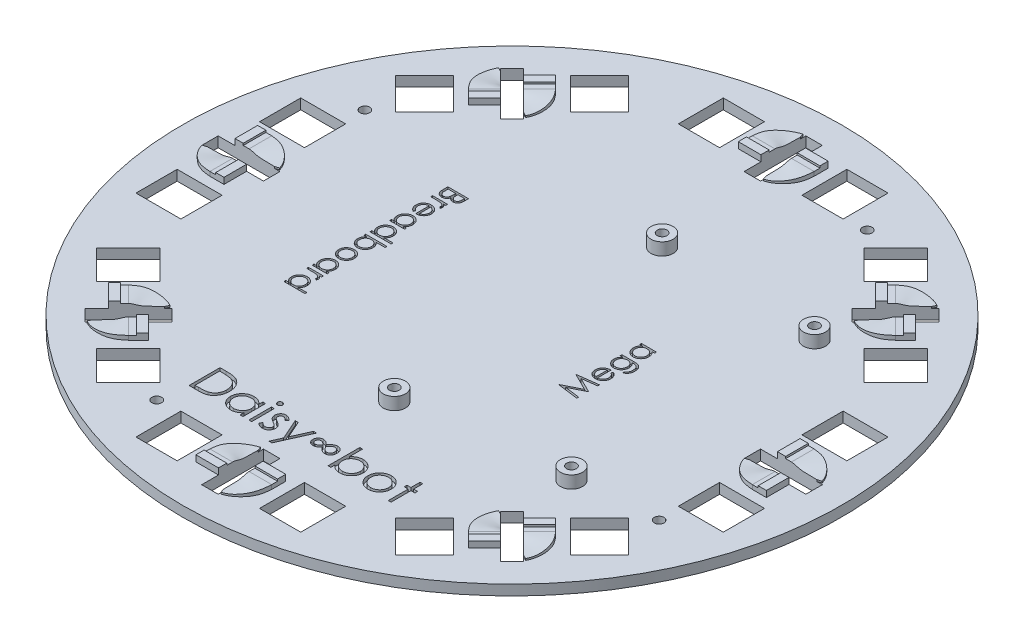
SolidWorks part; units mm, degrees
ref_plane "Front" through (0, 0, 0) normal (0, 0, 1) x (1, 0, 0)
ref_plane "Top" through (0, 0, 0) normal (0, 1, 0) x (1, 0, 0)
ref_plane "Right" through (0, 0, 0) normal (1, 0, 0) x (0, 0, -1)
sketch "Sketch1" plane through (0, 0, 0) normal (0, 1, 0) x (1, 0, 0)
  circle A0 centre (0, 0) radius 101.6
  dimension "D1" = 203.2
extrude "Base" add sketch "Sketch1" along normal blind 3.175 contours A0
sketch "Sketch2" plane through (0, 3.175, 0) normal (0, 1, 0) x (1, 0, 0)
  line L1 (-2.54, -93.1333) -> (2.54, -93.1333)
  line L2 (-2.54, -93.1333) -> (-2.54, -74.0833)
  line L3 (-2.54, -74.0833) -> (2.54, -74.0833)
  line L4 (2.54, -93.1333) -> (2.54, -74.0833)
  point P4 (0, -74.0833)
  dimension "D1" = 5.08
  dimension "D2" = 19.05
  dimension "D3" = 93.1333
extrude "Cut-Extrude1" cut sketch "Sketch2" against normal up to next and the other way through all contours L1 L4 L3 L2
sketch "Sketch4" plane through (0, 3.175, 0) normal (0, 1, 0) x (1, 0, 0)
  line L0 (0, -83.6083) -> (-2.9434, -74.5495) construction
  line L1 (-2.9434, -74.5495) -> (0, -83.6083) construction
  line L2 (0, -83.6083) -> (-5.5987, -75.9024) construction
  line L3 (0, -83.6083) -> (-7.7059, -78.0097) construction
  line L4 (0, -83.6083) -> (-9.0588, -80.6649) construction
  line L5 (0, -83.6083) -> (-9.525, -83.6083) construction
  line L9 (2.54, -74.0833) -> (-2.54, -74.0833) construction
  line L10 (2.54, -74.0833) -> (2.54, -93.1333) construction
  line L11 (-2.54, -74.0833) -> (-2.54, -93.1333) construction
  line L12 (2.54, -93.1333) -> (-2.54, -93.1333) construction
  circle A0 centre (0, -83.6083) radius 9.525 construction
  point P16 (0, -74.0833)
  point P19 (2.54, -83.6083)
  dimension "D1" = 18
  dimension "D2" = 18
  dimension "D3" = 18
  dimension "D4" = 18
  dimension "D5" = 18
ref_plane "Plane1" through (-24.5719, 0, 7.9839) normal (0.9511, 0, -0.309) x (-0.309, 0, -0.9511)
ref_plane "Plane2" through (-39.7581, 0, 28.886) normal (0.809, 0, -0.5878) x (-0.5878, 0, -0.809)
ref_plane "Plane3" through (-39.7581, 0, 54.7224) normal (0.5878, 0, -0.809) x (-0.809, 0, -0.5878)
ref_plane "Plane4" through (-24.5719, 0, 75.6244) normal (0.309, 0, -0.9511) x (-0.9511, 0, -0.309)
ref_plane "Plane5" through (0, 0, 83.6083) normal (0, 0, -1) x (-1, 0, 0)
sketch "Sketch5" plane through (-24.5719, 0, 7.9839) normal (0.9511, 0, -0.309) x (-0.309, 0, -0.9511)
  line L0 (-69.6725, 3.175) -> (-87.7902, 3.175) construction
  line L1 (-71.2966, 3.175) -> (-69.9913, 3.175)
  line L2 (-71.2966, 3.175) -> (-71.2966, 3.683)
  line L3 (-71.2966, 3.683) -> (-69.9913, 3.683)
  line L4 (-69.9913, 3.175) -> (-69.9913, 3.683)
  dimension "D2" = 0.508
sketch "Sketch6" plane through (-39.7581, 0, 28.886) normal (0.809, 0, -0.5878) x (-0.5878, 0, -0.809)
  line L0 (-58.4417, 3.175) -> (-73.8535, 3.175) construction
  line L1 (-63.3193, 3.175) -> (-58.1156, 3.175)
  line L2 (-63.3193, 3.175) -> (-63.3193, 3.775)
  line L3 (-63.3193, 3.775) -> (-58.1156, 3.775)
  line L4 (-58.1156, 3.175) -> (-58.1156, 3.775)
  dimension "D2" = 0.6
sketch "Sketch7" plane through (-39.7581, 0, 54.7224) normal (0.5878, 0, -0.809) x (-0.809, 0, -0.5878)
  line L0 (-41.4902, 3.175) -> (-52.6875, 3.175) construction
  line L1 (-46.0041, 3.175) -> (-39.6187, 3.175)
  line L2 (-46.0041, 3.175) -> (-46.0041, 4.075)
  line L3 (-46.0041, 4.075) -> (-39.6187, 4.075)
  line L4 (-39.6187, 3.175) -> (-39.6187, 4.075)
  dimension "D2" = 0.9
sketch "Sketch10" plane through (-24.5719, 0, 75.6244) normal (0.309, 0, -0.9511) x (-0.9511, 0, -0.309)
  line L0 (-25.8364, 3.175) -> (-16.7776, 3.175) construction
  line L1 (-23.1657, 3.175) -> (-16.3114, 3.175)
  line L2 (-23.1657, 3.175) -> (-23.1657, 4.375)
  line L3 (-23.1657, 4.375) -> (-16.3114, 4.375)
  line L4 (-16.3114, 3.175) -> (-16.3114, 4.375)
  dimension "D3" = 1.2
sketch "Sketch11" plane through (0, 0, 83.6083) normal (0, 0, -1) x (-1, 0, 0)
  line L0 (0, 3.175) -> (9.525, 3.175) construction
  line L1 (2.54, 3.175) -> (9.525, 3.175)
  line L2 (2.54, 3.175) -> (2.54, 4.475)
  line L3 (2.54, 4.475) -> (9.525, 4.475)
  line L4 (9.525, 3.175) -> (9.525, 4.475)
  dimension "D3" = 1.3
loft "Loft1" add profiles "Sketch5", "Sketch6", "Sketch7", "Sketch10", "Sketch11" connector at (-2.54, 3.683, 75.791) connector at (-2.54, 3.775, 80.1123) connector at (-2.54, 4.075, 81.7629) connector at (-2.54, 4.375, 82.783) connector at (-2.54, 4.475, 83.6083)
sketch "Sketch13" plane through (-104.9799, 0, 83.6083) normal (0, 0, -1) x (-1, 0, 0)
  line L6 (-95.4549, 3.175) -> (-102.4399, 3.175)
  line L7 (-95.4549, 3.175) -> (-95.4549, 4.475)
  line L8 (-95.4549, 4.475) -> (-102.4399, 4.475)
  line L9 (-102.4399, 3.175) -> (-102.4399, 4.475)
extrude "Boss-Extrude4" add sketch "Sketch13" against normal blind 1.7907
sketch "Sketch25" plane through (0, 0, 85.399) normal (0, 0, 1) x (1, 0, 0)
  line L0 (-9.525, 4.475) -> (-2.54, 4.475) construction
  line L1 (-9.525, 3.175) -> (-2.54, 3.175)
  line L2 (-9.525, 3.175) -> (-9.525, 5.075)
  line L3 (-9.525, 5.075) -> (-2.54, 5.075)
  line L4 (-2.54, 3.175) -> (-2.54, 5.075)
  dimension "D1" = 0.6
extrude "Boss-Extrude5" add sketch "Sketch25" along normal blind 2.54
sketch "Sketch14" plane through (-2.54, 0, 0) normal (1, 0, 0) x (0, 0, -1)
  line L0 (-83.6083, 3.175) -> (-83.6083, 0) construction
  line L1 (-74.0833, 0) -> (-93.1333, 0) construction
ref_plane "Plane6" through (0, 0, 0) normal (1, 0, 0) x (0, 0, -1)
sketch "Sketch15" plane through (0, 0, 0) normal (1, 0, 0) x (0, 0, -1)
  line L0 (-83.6083, 0) -> (-83.6083, 3.175) construction
pattern_circular "CirPattern1" count 2 over 360 about axis through (0, 0, 83.6083) along (0, 1, 0) of "Loft1", "Boss-Extrude5", "Boss-Extrude4" reverse direction yes
ref_axis "Axis1" through (0, 50, 0) along (0, -1, 0)
pattern_circular "CirPattern5" count 8 over 360 about axis through (0, 50, 0) along (0, -1, 0) of "CirPattern1", "Cut-Extrude1"
sketch "Sketch18" plane through (0, 3.175, 0) normal (0, 1, 0) x (1, 0, 0)
  line L0 (5, 41.275) -> (53.26, 41.275) construction
  line L1 (5, 41.275) -> (5, -41.275) construction
  line L2 (53.26, 41.275) -> (53.26, 40.005) construction
  line L3 (53.26, -34.925) -> (5, -34.925) construction
  line L4 (0, -101.6) -> (0, 101.6) construction
  line L5 (0, -1.7463) -> (0, 1.7463) construction
  line L6 (-101.6, 0) -> (101.6, 0) construction
  line L7 (53.26, 40.005) -> (53.26, -34.925) construction
  circle A0 centre (5, 41.275) radius 3.405
  circle A1 centre (5, -41.275) radius 3.405
  circle A2 centre (53.26, -34.925) radius 3.405
  circle A3 centre (53.26, 40.005) radius 3.405
  circle A4 centre (5, -41.275) radius 1.5
  circle A5 centre (5, 41.275) radius 1.5
  circle A6 centre (53.26, 40.005) radius 1.5
  circle A7 centre (53.26, -34.925) radius 1.5
  circle A8 centre (0, 0) radius 101.6 construction
  point P13 (0, 0)
  point P25 (0, 0)
  point P26 (0, 0)
  point P27 (0, 0)
  point P28 (10.3503, -35.3457)
  point P29 (5, 0)
  point P30 (0, 0)
  dimension "D7" = 1.905
  dimension "D8" = 3
  dimension "D9" = 1.27
  dimension "D1" = 82.55
  dimension "D2" = 74.93
  dimension "D3" = 5
  dimension "D10" = 48.26
sketch "Sketch19" plane through (0, 3.175, 0) normal (0, 1, 0) x (1, 0, 0)
  line L0 (-32.0765, -77.4396) -> (0, 0) construction
  line L1 (0, -101.6) -> (0, 101.6) construction
  circle A1 centre (-32.0765, -77.4396) radius 1.5
  circle A4 centre (0, 0) radius 101.6 construction
  dimension "D4" = 3
  dimension "D6" = 83.82
  dimension "D5" = 22.5
extrude "Cut-Extrude2" cut sketch "Sketch19" against normal through all
pattern_circular "CirPattern7" count 4 over 360 about axis through (0, 50, 0) along (0, -1, 0) of "Cut-Extrude2"
extrude "Mega_Screws" add sketch "Sketch18" along normal blind 3.81
sketch "Sketch23" plane through (0, 3.175, 0) normal (0, 1, 0) x (1, 0, 0)
  line L9 (-2.54, -87.939) -> (-2.54, -93.1333) construction
  line L10 (-25.4, -76.6805) -> (-12.7, -76.6805)
  line L11 (-25.4, -76.6805) -> (-25.4, -90.5362)
  line L16 (-25.4, -90.5362) -> (-12.7, -90.5362)
  line L17 (-12.7, -76.6805) -> (-12.7, -90.5362)
  line L19 (2.54, -74.0833) -> (2.54, -79.2776) construction
  line L20 (0, -50) -> (0, 50) construction
  line L21 (12.7, -76.6805) -> (12.7, -90.5362)
  line L22 (25.4, -90.5362) -> (12.7, -90.5362)
  line L23 (25.4, -76.6805) -> (25.4, -90.5362)
  line L24 (25.4, -76.6805) -> (12.7, -76.6805)
  point P8 (-2.54, -90.5362)
  point P9 (2.54, -76.6805)
  dimension "D1" = 12.7
  dimension "D2" = 10.16
extrude "Cut-Extrude6" cut sketch "Sketch23" against normal through all
pattern_circular "CirPattern8" count 8 over 360 about axis through (0, 50, 0) along (0, -1, 0) of "Cut-Extrude6"
sketch "Sketch17" plane through (0, 3.175, 0) normal (0, 1, 0) x (1, 0, 0)
  line L0 (33.02, -68.58) -> (-33.02, -68.58) construction
  line L1 (2.54, -74.0833) -> (-2.54, -74.0833) construction
  point P3 (0, -68.58)
  point P7 (0, -74.0833)
  dimension "D2" = 68.58
  dimension "D1" = 66.04
sketch "Sketch16" plane through (0, 3.175, 0) normal (0, 1, 0) x (1, 0, 0)
  line L0 (33.02, -68.58) -> (-33.02, -68.58) construction
  text T0 "Daisy∞bot\r\n" font "Century Gothic" height in points 36
extrude "Cut-Extrude4" cut sketch "Sketch16" against normal blind 1.27
sketch "Sketch22" plane through (0, 3.175, 0) normal (0, 1, 0) x (1, 0, 0)
  line L0 (-44.1287, 25.1735) -> (-44.1287, -33.6024) construction
  text T0 "Breadboard"
  point P3 (-44.1287, -4.2144)
extrude "Cut-Extrude5" cut sketch "Sketch22" against normal blind 1.27
sketch "Sketch24" plane through (0, 3.175, 0) normal (0, 1, 0) x (1, 0, 0)
  line L0 (32.161, -12.7) -> (32.161, 12.7) construction
  text T0 "Mega"
  point P2 (0, 0)
  point P4 (32.161, 0)
extrude "Cut-Extrude7" cut sketch "Sketch24" against normal blind 1.27
